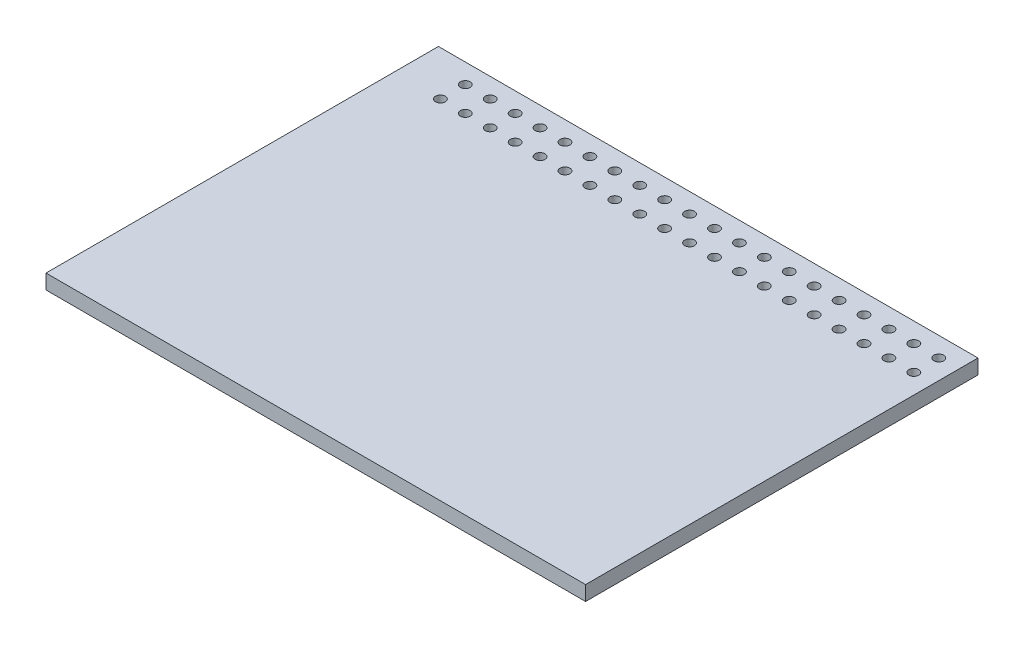
SolidWorks part; units mm, degrees
ref_plane "Front Plane" through (0, 0, 0) normal (0, 0, 1) x (1, 0, 0)
ref_plane "Top Plane" through (0, 0, 0) normal (0, 1, 0) x (1, 0, 0)
ref_plane "Right Plane" through (0, 0, 0) normal (1, 0, 0) x (0, 0, -1)
sketch "Sketch1" plane through (0, 0, 0) normal (0, 1, 0) x (1, 0, 0)
  line L1 (-27.5, -20) -> (27.5, -20)
  line L2 (-27.5, -20) -> (-27.5, 20)
  line L3 (-27.5, 20) -> (27.5, 20)
  line L4 (27.5, -20) -> (27.5, 20)
  line L5 (-27.5, -20) -> (27.5, 20) construction
  line L6 (-27.5, 20) -> (27.5, -20) construction
  circle A0 centre (25.5, 18) radius 0.5
  circle A1 centre (22.96, 18) radius 0.5
  circle A2 centre (20.42, 18) radius 0.5
  circle A3 centre (17.88, 18) radius 0.5
  circle A4 centre (15.34, 18) radius 0.5
  circle A5 centre (12.8, 18) radius 0.5
  circle A6 centre (10.26, 18) radius 0.5
  circle A7 centre (7.72, 18) radius 0.5
  circle A8 centre (5.18, 18) radius 0.5
  circle A9 centre (2.64, 18) radius 0.5
  circle A10 centre (0.1, 18) radius 0.5
  circle A11 centre (-2.44, 18) radius 0.5
  circle A12 centre (-4.98, 18) radius 0.5
  circle A13 centre (-7.52, 18) radius 0.5
  circle A14 centre (-10.06, 18) radius 0.5
  circle A15 centre (-12.6, 18) radius 0.5
  circle A16 centre (-15.14, 18) radius 0.5
  circle A17 centre (-17.68, 18) radius 0.5
  circle A18 centre (-20.22, 18) radius 0.5
  circle A19 centre (-22.76, 18) radius 0.5
  circle A20 centre (22.96, 15.46) radius 0.5
  circle A21 centre (20.42, 15.46) radius 0.5
  circle A22 centre (17.88, 15.46) radius 0.5
  circle A23 centre (15.34, 15.46) radius 0.5
  circle A24 centre (12.8, 15.46) radius 0.5
  circle A25 centre (10.26, 15.46) radius 0.5
  circle A26 centre (7.72, 15.46) radius 0.5
  circle A27 centre (5.18, 15.46) radius 0.5
  circle A28 centre (2.64, 15.46) radius 0.5
  circle A29 centre (0.1, 15.46) radius 0.5
  circle A30 centre (-2.44, 15.46) radius 0.5
  circle A31 centre (-4.98, 15.46) radius 0.5
  circle A32 centre (-7.52, 15.46) radius 0.5
  circle A33 centre (-10.06, 15.46) radius 0.5
  circle A34 centre (-12.6, 15.46) radius 0.5
  circle A35 centre (-15.14, 15.46) radius 0.5
  circle A36 centre (-17.68, 15.46) radius 0.5
  circle A37 centre (-20.22, 15.46) radius 0.5
  circle A38 centre (-22.76, 15.46) radius 0.5
  circle A39 centre (25.5, 15.46) radius 0.5
  point P0 (0, 0)
  dimension "D3" = 1
  dimension "D1" = 40
  dimension "D2" = 55
  dimension "D4" = 2
  dimension "D5" = 2
  dimension "D8" = 2.54
  dimension "D9" = 2.54
  dimension "D6" = 20
  dimension "D7" = 2
extrude "Boss-Extrude1" add sketch "Sketch1" along normal blind 1.5
